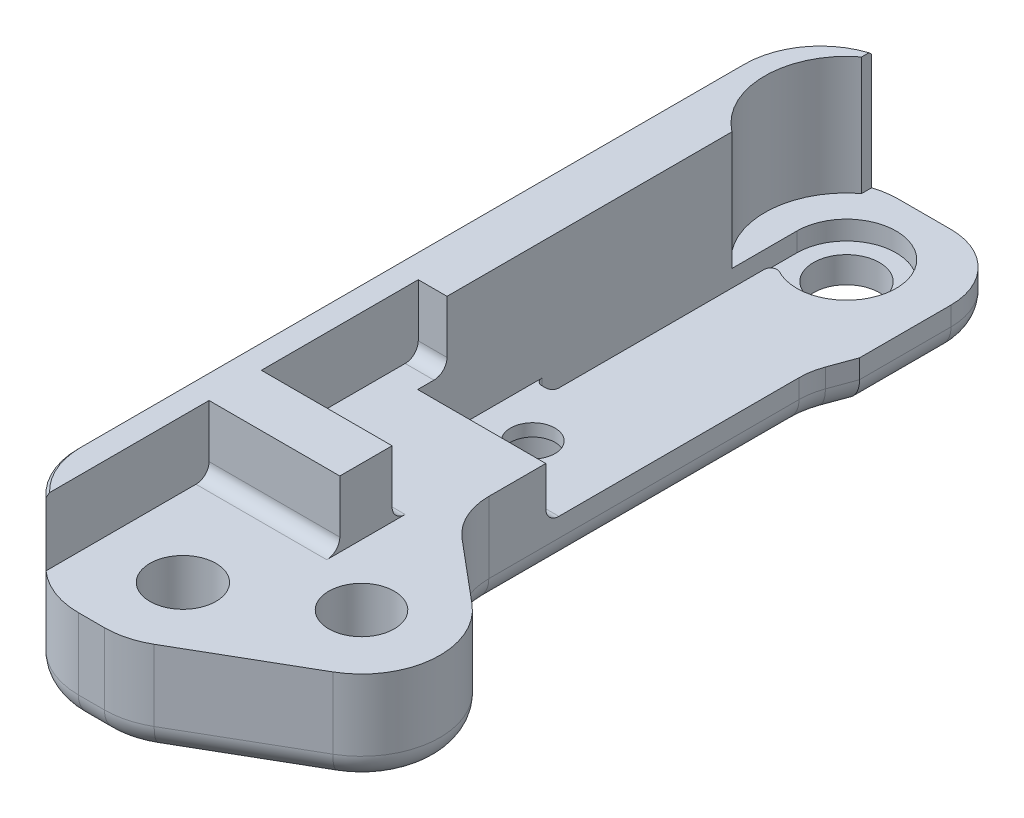
SolidWorks part; units mm, degrees
ref_plane "前视基准面" through (0, 0, 0) normal (0, 0, 1) x (1, 0, 0)
ref_plane "上视基准面" through (0, 0, 0) normal (0, 1, 0) x (1, 0, 0)
ref_plane "右视基准面" through (0, 0, 0) normal (1, 0, 0) x (0, 0, -1)
other "Configuration Table"
sketch "草图1" plane through (0, 0, 0) normal (0, 1, 0) x (1, 0, 0)
  line L0 (0, 0) -> (0, 50.7543) construction
  line L1 (-8, -6) -> (-8, 56.7543)
  line L2 (-8, 56.7543) -> (7, 56.7543)
  line L3 (7, 56.7543) -> (7, 44.7543)
  line L4 (7, 44.7543) -> (6, 42.0068)
  line L5 (6, 42.0068) -> (6, 15.0647)
  line L8 (0, -6) -> (-8, -6)
  line L9 (8.6603, 5) -> (0, 0) construction
  line L10 (18.5622, 5) -> (8.6603, 5) construction
  line L11 (11.6603, -0.1962) -> (3, -5.1962)
  line L12 (6, 15.0647) -> (12.517, 9.5963)
  circle A1 centre (0, 0) radius 2.525
  circle A2 centre (0, 50.7543) radius 2.525
  circle A3 centre (8.6603, 5) radius 2.505
  arc A4 (11.6603, -0.1962) -> (12.517, 9.5963) centre (8.6603, 5) ccw
  arc A5 (0, -6) -> (3, -5.1962) centre (0, 0) ccw
  dimension "D1" = 5.05
  dimension "D3" = 5.05
  dimension "D9" = 5.01
  dimension "D8" = 12
  dimension "D14" = 12
  dimension "D2" = 50.7543
  dimension "D4" = 6
  dimension "D5" = 6
  dimension "D6" = 8
  dimension "D7" = 7
  dimension "D10" = 30
  dimension "D11" = 14
  dimension "D12" = 12
  dimension "D13" = 10
  dimension "D15" = 20
  dimension "D16" = 50
extrude "凸台-拉伸1" add sketch "草图1" along normal blind 25
ref_plane "基准面2" through (0, 12.5, 0) normal (0, -1, 0) x (-1, 0, 0)
sketch "草图6" plane through (0, 12.5, 0) normal (0, -1, 0) x (-1, 0, 0)
  line L0 (8, 56.7543) -> (8, -6) construction
  line L1 (-7, 56.7543) -> (3.8, 56.7543)
  line L2 (-7, 56.7543) -> (-7, 21.7543)
  line L3 (-7, 21.7543) -> (3.8, 21.7543)
  line L4 (3.8, 56.7543) -> (3.8, 21.7543)
  dimension "D1" = 4.2
  dimension "D2" = 35
extrude "切除-拉伸2" cut sketch "草图6" against normal mid plane 18.1
sketch "草图5" plane through (0, 12.5, 0) normal (0, -1, 0) x (-1, 0, 0)
  line L0 (8, -6) -> (0, -6) construction
  line L1 (-19, 24) -> (6, 24)
  line L2 (-19, 24) -> (-19, -6)
  line L3 (-19, -6) -> (6, -6)
  line L4 (6, 24) -> (6, -6)
  line L5 (8, 56.7543) -> (8, -6) construction
  dimension "D1" = 2
  dimension "D2" = 30
  dimension "D3" = 25
extrude "切除-拉伸1" cut sketch "草图5" against normal mid plane 10.1
fillet "圆角2" radius 6 2 edges at (-8, 12.5, 6) (-8, 12.5, -56.7543)
sketch "草图7" plane through (0, 7.45, 0) normal (0, 1, 0) x (1, 0, 0)
  circle A0 centre (0, 0) radius 5
  circle A1 centre (0, 0) radius 2.5
  dimension "D1" = 10
  dimension "D2" = 5
sketch "草图8" plane through (0, 17.55, 0) normal (0, -1, 0) x (1, 0, 0)
  circle A0 centre (0, 0) radius 5
  circle A1 centre (0, 0) radius 2.5
  dimension "D1" = 10
  dimension "D2" = 5
fillet "圆角4" radius 5 6 edges at (7, 1.725, -56.7543) (7, 23.275, -56.7543) (6, 3.725, -15.0647) (6, 1.725, -42.0068) (6, 23.275, -42.0068) (6, 21.275, -15.0647)
fillet "圆角7" radius 2 30 edges at (7, 0, -48.2543) (5.5355, 0, -55.2898) (0, 0, -56.7543) (-6.2426, 0, -54.997) (10.1515, 0, -11.5811) (14.6374, 0, -4.4771) (7.3301, 0, 2.6962) (1.5529, 0, 5.7956) (-1, 0, 6) (-6.2426, 0, 4.2426) (7, 25, -48.2543) (5.5355, 25, -55.2898) (0, 25, -56.7543) (-6.2426, 25, -54.997) (10.1515, 25, -11.5811) (14.6374, 25, -4.4771) (7.3301, 25, 2.6962) (1.5529, 25, 5.7956) (-1, 25, 6) (-6.2426, 25, 4.2426) (6.6508, 0, -43.7948) (-8, 0, -25.3772) (6, 0, -29.2607) (6.6508, 25, -43.7948) (6, 25, -29.2607) (-8, 25, -25.3772) (6.4685, 0, -15.2831) (6.076, 0, -41.9934) (6.076, 25, -41.9934) (6.4685, 25, -15.2831)
sketch "草图9" plane through (-6, 0, 0) normal (1, 0, 0) x (0, 0, -1)
  line L0 (13.566, 17.55) -> (9.5963, 17.55) construction
  line L1 (8, 17.55) -> (12, 17.55)
  line L2 (8, 17.55) -> (8, 7.45)
  line L3 (8, 7.45) -> (12, 7.45)
  line L4 (12, 17.55) -> (12, 7.45)
  line L5 (17.3962, 7.45) -> (13.566, 7.45) construction
  line L6 (24, 17.55) -> (24, 7.45) construction
  dimension "D1" = 12
  dimension "D2" = 4
extrude "凸台-拉伸4" add sketch "草图9" along normal blind 10
ref_plane "基准面3" through (0, 12.5, 0) normal (0, -1, 0) x (-1, 0, 0)
fillet "圆角8" radius 1 8 edges at (1.1, 3.45, -21.7543) (-1, 7.45, -12) (-4.9, 7.45, -24) (-1, 7.45, -8) (-1, 17.55, -8) (1.1, 21.55, -21.7543) (-1, 17.55, -12) (-4.9, 17.55, -24)
sketch "草图11" plane through (0, 12.5, 0) normal (0, -1, 0) x (-1, 0, 0)
  line L1 (-26.7164, 62.0414) -> (24.7804, 62.0414)
  line L2 (-26.7164, 62.0414) -> (-26.7164, -8.5902)
  line L3 (-26.7164, -8.5902) -> (24.7804, -8.5902)
  line L4 (24.7804, 62.0414) -> (24.7804, -8.5902)
extrude "切除-拉伸5" cut sketch "草图11" against normal blind 22
chamfer "倒角1" distance 0.2 angle 45 3 edges at (-7.4772, 12.5, 2.4495) (-6.8374, 12.5, -54.304) (-8, 12.5, -25.3772)
sketch "草图14" plane through (0, 12.5, 0) normal (0, 1, 0) x (1, 0, 0)
  circle A0 centre (0, 50.7543) radius 6.25
  dimension "D1" = 12.5
extrude "切除-拉伸8" cut sketch "草图14" against normal up to surface (9.05 mm away) up to face at (0, 3.45, -53.2793)
sketch "草图16" plane through (0, 3.45, 0) normal (0, 1, 0) x (1, 0, 0)
  line L1 (-3.8, 45.7922) -> (-3.8, 24) construction
  line L2 (-3.8, 50.7543) -> (-3.8, 30.7543)
  line L3 (-3.8, 22.7543) -> (-3.8, 45.7922) construction
  line L4 (-3.8, 30.7543) -> (-2.5, 30.7543)
  line L5 (-2.5, 30.7543) -> (-2.5, 47.8925)
  arc A0 (-2.5, 47.8925) -> (-3.8, 50.7543) centre (0, 50.7543) ccw
  dimension "D1" = 1.3
  dimension "D2" = 20
extrude "切除-拉伸9" cut sketch "草图16" against normal blind 1.45
fillet "圆角9" radius 0.5 1 edges at (-2.5, 2.725, -47.8925)
fillet "圆角10" radius 0.5 2 edges at (-2.5, 2.725, -30.7543) (-3.8, 2.725, -30.7543)
sketch "草图17" plane through (0, 3.45, 0) normal (0, 1, 0) x (1, 0, 0)
  line L0 (6, 41.1252) -> (6, 22.7543) construction
  line L1 (-3.8, 21.7543) -> (6, 21.7543) construction
  circle A0 centre (0, 26.7543) radius 1.7
  dimension "D1" = 3.4
  dimension "D2" = 6
  dimension "D3" = 5
extrude "切除-拉伸10" cut sketch "草图17" against normal blind 10
sketch "草图18" plane through (0, 0, 0) normal (0, -1, 0) x (1, 0, 0)
  circle A0 centre (0, -26.7543) radius 3
  dimension "D1" = 6
extrude "切除-拉伸11" cut sketch "草图18" against normal blind 2.5
